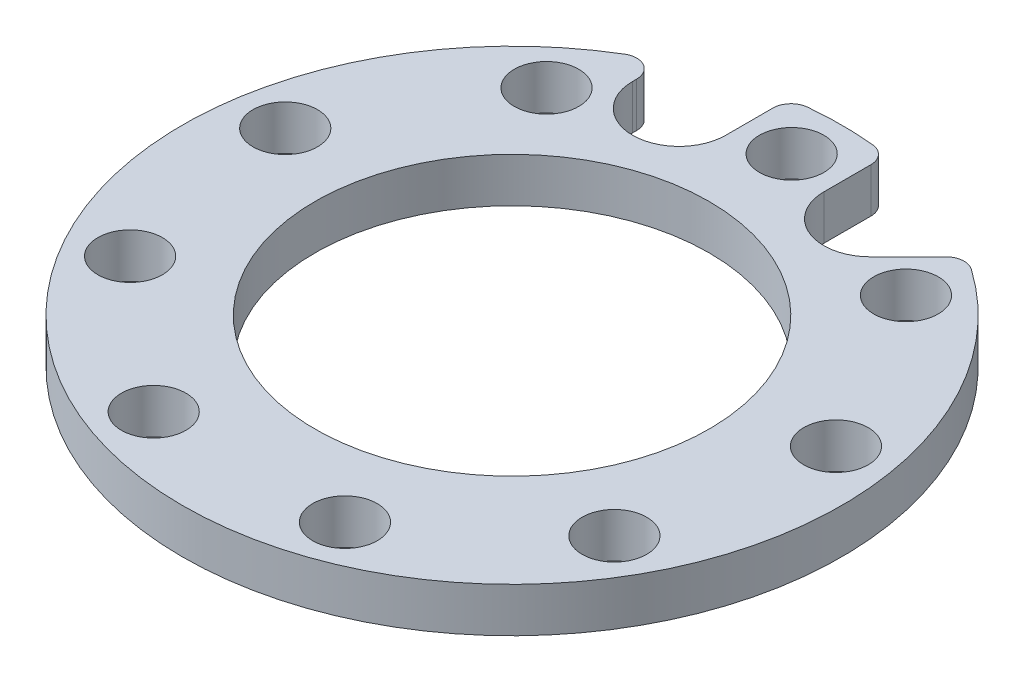
SolidWorks part; units mm, degrees
material "6061-T6 (SS)"
ref_plane "X-Y Datum" through (0, 0, 0) normal (0, 0, 1) x (1, 0, 0)
ref_plane "X-Z Datum" through (0, 0, 0) normal (0, 1, 0) x (1, 0, 0)
ref_plane "Y-Z Datum" through (0, 0, 0) normal (1, 0, 0) x (0, 0, -1)
sketch "Sketch1" plane through (0, 0, 0) normal (0, 1, 0) x (1, 0, 0)
  circle A0 centre (0, 0) radius 45.974
  circle A1 centre (0, 0) radius 39 construction
  circle A2 centre (0, 0) radius 25.908 construction
  circle A3 centre (0, 0) radius 27.4955
  circle A6 centre (-13.3388, 36.648) radius 6.5
  circle A7 centre (13.3388, 36.648) radius 6.5
  point P7 (0, 39)
  point P11 (13.3388, 36.648)
  point P12 (25.0687, 29.8757)
  point P13 (33.775, 19.5)
  point P14 (38.4075, 6.7723)
  point P15 (38.4075, -6.7723)
  point P16 (33.775, -19.5)
  point P17 (25.0687, -29.8757)
  point P18 (13.3388, -36.648)
  point P19 (0, -39)
  point P20 (-13.3388, -36.648)
  point P21 (-25.0687, -29.8757)
  point P22 (-33.775, -19.5)
  point P23 (-38.4075, -6.7723)
  point P24 (-38.4075, 6.7723)
  point P25 (-33.775, 19.5)
  point P26 (-25.0687, 29.8757)
  point P27 (-13.3388, 36.648)
  point P28 (0, 0)
  dimension "D1" = 91.948
  dimension "D2" = 78
  dimension "D3" = 51.816
  dimension "D6" = 13
  dimension "D4" = 1.5875
  dimension "D5" = 18
extrude "Boss-Extrude1" add sketch "Sketch1" along normal blind 6.214
hole_wizard "M8 Clearance Hole1" positions "Sketch4" profile "Sketch5" hole size "M8" standard "ANSI Metric" end condition through all
sketch "Sketch4" plane through (0, 6.214, 0) normal (0, 1, 0) x (1, 0, 0)
  point P0 (0, 39)
sketch "Sketch5" plane through (0, 6.214, -39) normal (1, 0, 0) x (0, 0, 1)
  line L0 (0, 0) -> (0, 6.214)
  line L1 (0, 6.214) -> (4.5, 6.214)
  line L2 (4.5, 6.214) -> (4.5, 0)
  line L5 (4.5, 0) -> (0, 0)
  line L11 (0, -6.35) -> (0, 107.95) construction
  dimension "Thru Hole Dia." = 9
  dimension "Thru Hole Depth" = 6.214
pattern_circular "CirPattern1" count 9 over 360 about axis through (0, 6.214, 0) along (0, -1, 0) of "M8 Clearance Hole1"
sketch "Sketch6" plane through (0, 6.214, 0) normal (0, 1, 0) x (1, 0, 0)
  line L0 (17.935, 32.0518) -> (24.6746, 38.7914)
  line L1 (6.8388, 36.648) -> (6.8388, 45.4625)
  line L2 (-6.8388, 36.648) -> (-6.8388, 45.4625)
  line L4 (-19.8388, 36.648) -> (-19.8388, 41.4733)
  circle A0 centre (-13.3388, 36.648) radius 6.5 construction
  circle A1 centre (13.3388, 36.648) radius 6.5 construction
  circle A2 centre (-13.3388, 36.648) radius 6.5 construction
  circle A3 centre (13.3388, 36.648) radius 6.5 construction
  circle A4 centre (0, 0) radius 45.974 construction
  arc A8 (6.8388, 45.4625) -> (24.6746, 38.7914) centre (0, 0) cw
  arc A10 (6.8388, 36.648) -> (17.935, 32.0518) centre (13.3388, 36.648) cw
  arc A11 (-19.8388, 36.648) -> (-6.8388, 36.648) centre (-13.3388, 36.648) cw
  arc A12 (-19.8388, 41.4733) -> (-6.8388, 45.4625) centre (0, 0) cw
  dimension "D2" = 6.7396
extrude "Cut-Extrude1" cut sketch "Sketch6" against normal through all
fillet "Fillet1" radius 2.54 4 edges at (24.6746, 3.107, -38.7914) (6.8388, 3.107, -45.4625) (-6.8388, 3.107, -45.4625) (-19.8388, 3.107, -41.4733)
